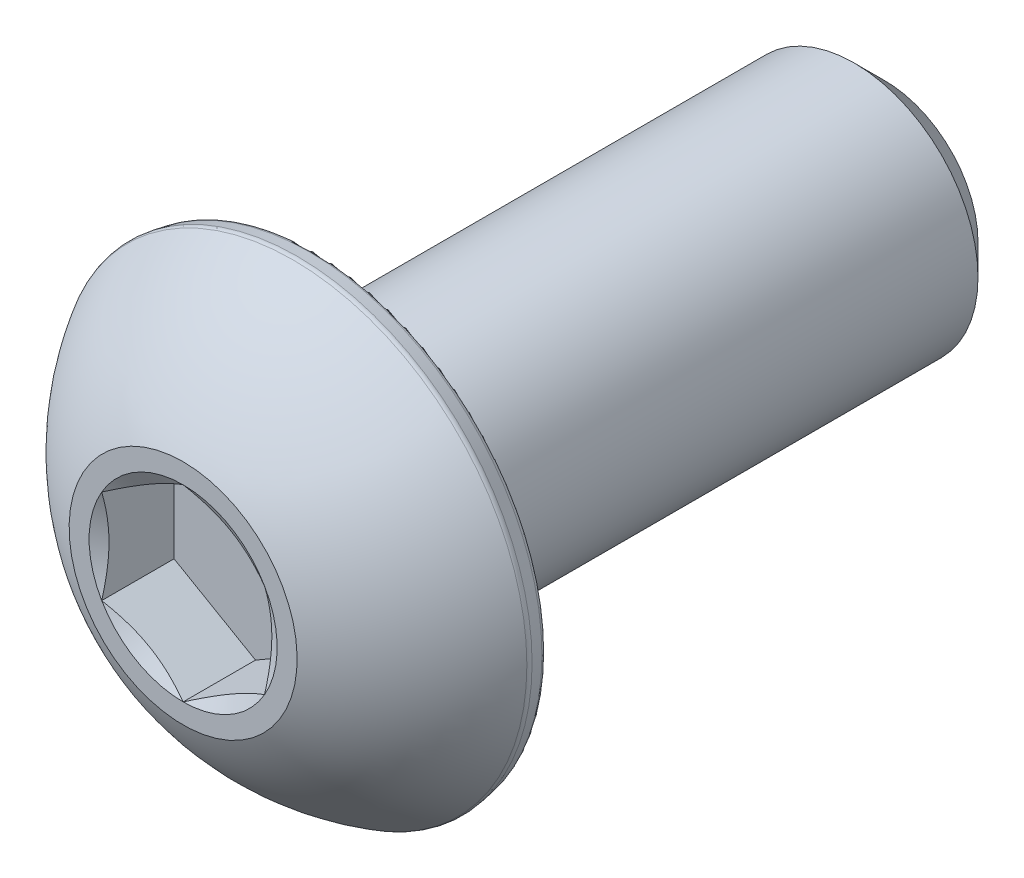
SolidWorks part; units mm, degrees
material "Alloy Steel"
ref_plane "Front Plane" through (0, 0, 0) normal (0, 0, 1) x (1, 0, 0)
ref_plane "Top Plane" through (0, 0, 0) normal (0, 1, 0) x (1, 0, 0)
ref_plane "Right Plane" through (0, 0, 0) normal (1, 0, 0) x (0, 0, -1)
sketch "Sketch1" plane through (0, 0, 0) normal (1, 0, 0) x (0, 0, -1)
  line L0 (-6.8389, 0) -> (6.8389, 0) construction
  line L1 (-6.8389, 0) -> (-6.8389, 4.5847)
  line L2 (-6.8389, 4.5847) -> (-4.2735, 4.5847)
  line L3 (-4.2735, 4.5847) -> (-4.2735, 2.413)
  line L4 (-4.2735, 2.413) -> (6.8389, 2.413)
  line L5 (6.8389, 2.413) -> (6.8389, 0)
  point P2 (0, 0)
  point P4 (6.0452, 0)
  point P9 (5.6483, 2.413)
  point P10 (5.6483, -2.413)
  point P11 (6.8389, -2.413)
  point P15 (-5.428, 0)
  dimension "Head Height" = 2.5654
  dimension "Head Diameter" = 9.1694
  dimension "Length" = 11.1125
  dimension "Screw Size Decimal Equivalent" = 4.826
  dimension "Thread Pitch" = 0.7937
  dimension "D1" = 1.1906
  dimension "D2" = 1.411
sketch "Sketch2" plane through (0, 0, 0) normal (0, 0, 1) x (1, 0, 0)
  line L0 (0, 2.413) -> (0, 0) construction
  line L1 (0, 1.8331) -> (-1.5875, 0.9165)
  line L2 (-1.5875, 0.9165) -> (-1.5875, -0.9165)
  line L3 (-1.5875, -0.9165) -> (0, -1.8331)
  line L4 (0, -1.8331) -> (1.5875, -0.9165)
  line L5 (1.5875, -0.9165) -> (1.5875, 0.9165)
  line L6 (1.5875, 0.9165) -> (0, 1.8331)
  circle A0 centre (0, 0) radius 1.5875 construction
  circle A1 centre (0, 0) radius 2.2225
  point P10 (0, 2.2225)
  dimension "D1" = 4.445
  dimension "Drive Size" = 3.175
sketch "Sketch3" plane through (0, 0, 0) normal (1, 0, 0) x (0, 0, -1)
  line L0 (-6.8389, 0) -> (-6.8389, 2.2225)
  line L1 (-6.8389, 0) -> (-6.8389, 4.5847) construction
  line L2 (-6.8389, 4.5847) -> (-4.2735, 4.5847) construction
  line L3 (-4.6584, 4.5847) -> (-4.2735, 4.5168)
  line L4 (-4.2735, 4.5847) -> (-4.2735, 2.413) construction
  line L5 (-4.2735, 4.5168) -> (-4.2735, 2.413)
  line L6 (-6.8389, 0) -> (6.8389, 0) construction
  line L7 (-6.8389, 0) -> (6.8389, 0)
  line L8 (6.8389, 0) -> (6.8389, 1.8177)
  line L9 (6.8389, 2.413) -> (6.8389, 0) construction
  line L10 (6.8389, 1.8177) -> (6.2436, 2.413)
  line L11 (-4.2735, 2.413) -> (6.8389, 2.413) construction
  line L12 (6.2436, 2.413) -> (-4.2735, 2.413)
  arc A0 (-6.8389, 2.2225) -> (-4.6584, 4.5847) centre (-2.0616, 0) cw
  dimension "D1" = 0.3848
  dimension "D2" = 10
  dimension "D3" = 45
  dimension "D4" = 0.5953
revolve "Revolve1" add sketch "Sketch3" angle 360 about L7
sketch "Sketch4" plane through (0, 0, 6.8389) normal (0, 0, 1) x (1, 0, 0)
  line L0 (-1.5875, -0.9165) -> (0, -1.8331) construction
  line L1 (-1.5875, 0.9165) -> (-1.5875, -0.9165) construction
  line L2 (0, 1.8331) -> (-1.5875, 0.9165) construction
  line L3 (1.5875, 0.9165) -> (0, 1.8331) construction
  line L4 (1.5875, -0.9165) -> (1.5875, 0.9165) construction
  line L5 (0, -1.8331) -> (1.5875, -0.9165) construction
  line L6 (-1.5875, -0.9165) -> (0, -1.8331)
  line L7 (-1.5875, 0.9165) -> (-1.5875, -0.9165)
  line L8 (0, 1.8331) -> (-1.5875, 0.9165)
  line L9 (1.5875, 0.9165) -> (0, 1.8331)
  line L10 (1.5875, -0.9165) -> (1.5875, 0.9165)
  line L11 (0, -1.8331) -> (1.5875, -0.9165)
extrude "Cut-Extrude1" cut sketch "Sketch4" against normal up to vertex (1.411 mm away) up to point (0, 0, 5.428)
sketch "Sketch5" plane through (0, 0, 6.8389) normal (0, 0, 1) x (1, 0, 0)
  circle A0 centre (0, 0) radius 1.8331
extrude "Cut-Extrude2" cut sketch "Sketch5" against normal up to vertex (1.411 mm away) draft 60 up to point (0, 0, 5.428)
fillet "Fillet1" radius 0.1283 2 edges at (4.5847, 0, 4.6584) (4.5168, 0, 4.2735)
split "Split1" [suppressed] bodies to split 106
sketch "Sketch6" [suppressed] plane through (0, 0, -7.6327) normal (0, 0, -1) x (-1, 0, 0)
  circle A0 centre (0, 0) radius 2.413 construction
  circle A1 centre (0, 0) radius 2.413
curve "Helix/Spiral1" [suppressed]
sketch "Sketch7" [suppressed] plane through (0, 0, 0) normal (1, 0, 0) x (0, 0, -1)
  line L0 (7.5831, 2.4989) -> (7.98, 1.8115) construction
  line L1 (7.98, 1.8115) -> (8.3768, 2.4989) construction
  line L2 (8.3768, 2.4989) -> (7.5831, 2.4989) construction
  line L3 (7.6079, 2.456) -> (8.352, 2.456)
  line L4 (8.352, 2.456) -> (8.0296, 1.8974)
  line L5 (8.0296, 1.8974) -> (7.9304, 1.8974)
  line L6 (7.9304, 1.8974) -> (7.6079, 2.456)
  line L7 (7.98, 1.8974) -> (7.98, 1.8115) construction
  line L8 (7.6327, 2.413) -> (8.3272, 2.413) construction
  line L9 (7.98, 2.4989) -> (7.98, 2.413) construction
  point P12 (7.98, 2.456)
  dimension "D1" = 0.7937
  dimension "D2" = 0.0992
sweep "Cut-Sweep1" [suppressed] cut profiles "Sketch7" path "Helix/Spiral1"
sketch "Sketch8" [suppressed] plane through (0, 0, 5.0673) normal (0, 0, -1) x (-1, 0, 0)
  circle A0 centre (0, 0) radius 2.4989
extrude "Boss-Extrude1" [suppressed] add sketch "Sketch8" along normal up to vertex draft 45
equation "\"D1@Sketch1\"=\"Thread Pitch@Sketch1\"*1.5"
equation "\"D2@Sketch1\"=0.55*\"Head Height@Sketch1\""
equation "\"D1@Sketch2\"=\"Drive Size@Sketch2\"*1.4"
equation "\"D1@Sketch3\"=0.15*\"Head Height@Sketch1\""
equation "\"D4@Sketch3\"=0.75*\"Thread Pitch@Sketch1\""
equation "\"D1@Fillet1\"=.05*\"Head Height@Sketch1\""
equation "\"D4@Helix/Spiral1\"=\"Thread Pitch@Sketch1\""
equation "\"D3@Helix/Spiral1\"=\"Length@Sketch1\"+\"Thread Pitch@Sketch1\""
equation "\"D2@Sketch7\"=\"D1@Sketch7\"/8"
equation "\"D1@Sketch7\"=\"Thread Pitch@Sketch1\""
